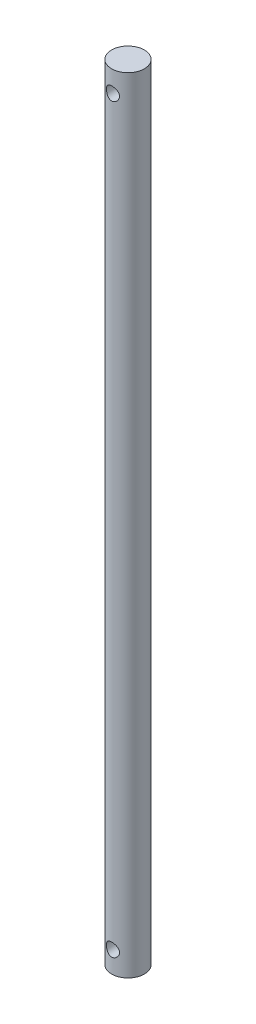
SolidWorks part; units mm, degrees
ref_plane "Alzado" through (0, 0, 0) normal (0, 0, 1) x (1, 0, 0)
ref_plane "Planta" through (0, 0, 0) normal (0, 1, 0) x (1, 0, 0)
ref_plane "Vista lateral" through (0, 0, 0) normal (1, 0, 0) x (0, 0, -1)
sketch "Croquis1" plane through (0, 0, 0) normal (0, 1, 0) x (1, 0, 0)
  circle A0 centre (0, 0) radius 5
  dimension "D1" = 10
extrude "Saliente-Extruir1" add sketch "Croquis1" along normal blind 339
sketch "Croquis2" plane through (0, 339, 0) normal (0, 1, 0) x (1, 0, 0)
  circle A0 centre (0, 0) radius 6.8947
extrude "Cortar-Extruir1" cut sketch "Croquis2" against normal blind 99.5
sketch "Croquis3" plane through (0, 0, 0) normal (0, 0, 1) x (1, 0, 0)
  line L0 (0, 0) -> (0, 6.5) construction
  circle A0 centre (0, 6.5) radius 2
  dimension "D2" = 4
  dimension "D1" = 6.5
extrude "Cortar-Extruir2" cut sketch "Croquis3" against normal blind 10 and the other way blind 10
sketch "Croquis4" plane through (0, 0, 0) normal (0, 0, 1) x (1, 0, 0)
  line L0 (0, 239.5) -> (0, 229.7609) construction
  line L3 (5, 239.5) -> (-5, 239.5) construction
  circle A0 centre (0, 233) radius 2
  dimension "D2" = 4
  dimension "D1" = 6.5
extrude "Cortar-Extruir3" cut sketch "Croquis4" against normal blind 10 and the other way blind 10
